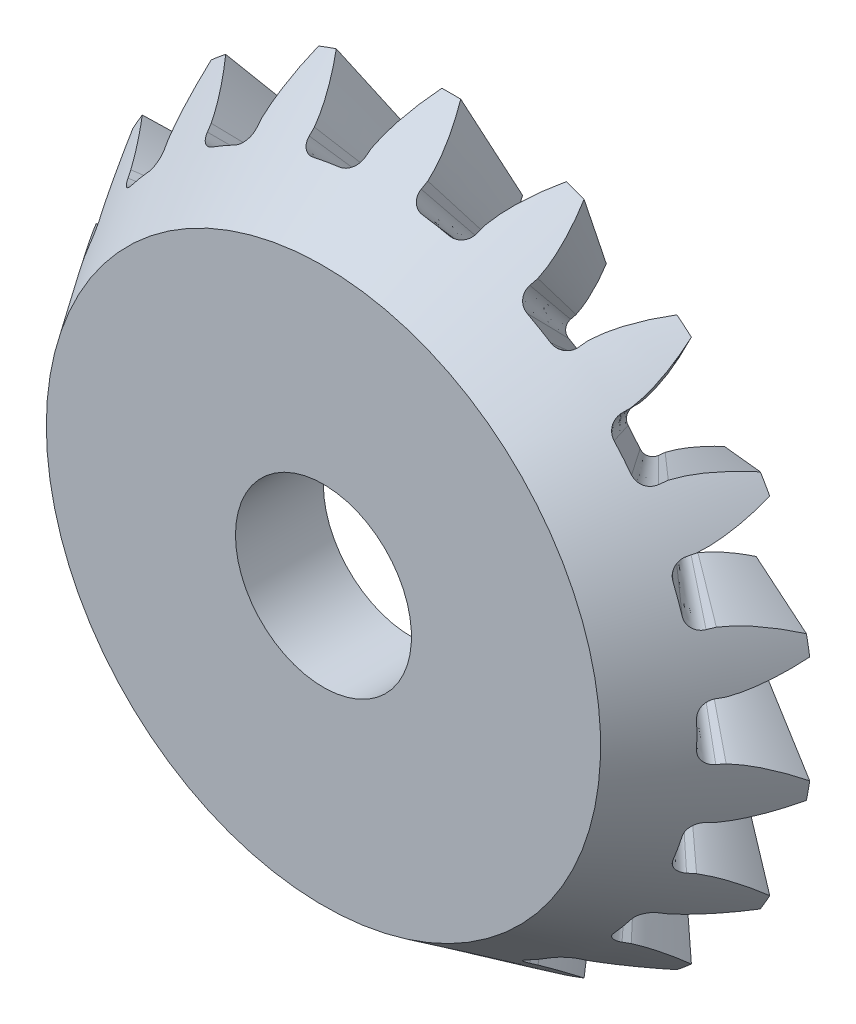
SolidWorks part; units mm, degrees
ref_plane "Front Plane" through (0, 0, 0) normal (0, 0, 1) x (1, 0, 0)
ref_plane "Top Plane" through (0, 0, 0) normal (0, 1, 0) x (1, 0, 0)
ref_plane "Right Plane" through (0, 0, 0) normal (1, 0, 0) x (0, 0, -1)
ref_axis "Gear Axis" through (0, 0, -0.9465) along (0, 0, 1)
sketch "Blank Sketch" plane through (0, 0, 0) normal (0, 1, 0) x (1, 0, 0)
  line L0 (0, 0) -> (0, -18.9291) construction
  line L1 (0, 0) -> (15.75, -10.5) construction
  line L2 (0, 0) -> (10.7577, -7.1718) construction
  line L3 (8.0506, -11.2325) -> (11.1934, -6.5182)
  line L4 (11.1934, -6.5182) -> (16.4727, -9.416)
  line L5 (16.4727, -9.416) -> (12.5987, -15.2269)
  line L6 (12.5987, -15.2269) -> (4, -15.2269)
  line L7 (4, -15.2269) -> (4, -11.2325)
  line L8 (4, -11.2325) -> (8.0506, -11.2325)
  line L9 (15.75, -10.5) -> (16.4727, -9.416) construction
  line L10 (15.75, -10.5) -> (12.5987, -15.2269) construction
  line L11 (10.7577, -7.1718) -> (8.0506, -11.2325) construction
  dimension "Axis" = 18.9291
  dimension "Cone" = 56.31
  dimension "Heel" = 18.9291
  dimension "Toe Cone" = 56.31
  dimension "Toe" = 12.9291
  dimension "Heel Square" = 90
  dimension "Addendum" = 1.3028
  dimension "Root Square" = 90
  dimension "Heel Rim" = 5.6811
  dimension "Toe Square" = 90
  dimension "Toe Rim" = 4.8803
  dimension "Front Square" = 90
  dimension "Face" = 4.927
  dimension "Back" = 8.5987
  dimension "Front" = 4.0506
revolve "Blank" add sketch "Blank Sketch" angle 360 about L0
sketch "Cone Sketch" plane through (0, 0, 0) normal (0, 1, 0) x (1, 0, 0)
  line L0 (0, 0) -> (0, -18.9291) construction
  line L1 (0, 0) -> (17.2061, -11.4707)
  line L2 (0, 0) -> (9.3016, -6.2011)
  dimension "Axis" = 18.9291
  dimension "Toe Cone" = 56.31
  dimension "Heel Cone" = 56.31
  dimension "Heel" = 20.6791
  dimension "Toe" = 11.1791
ref_plane "Heel Plane" through (17.2061, 0, 11.4707) normal (0.8321, 0, 0.5547) x (0.5547, 0, -0.8321)
ref_plane "Toe Plane" through (9.3016, 0, 6.2011) normal (0.8321, 0, 0.5547) x (0.5547, 0, -0.8321)
sketch "Heel Section Sketch" plane through (17.2061, 0, 11.4707) normal (0.8321, 0, 0.5547) x (0.5547, 0, -0.8321)
  line L0 (0, 0) -> (-31.0187, 0) construction
  line L1 (-1.7053, 1.438) -> (-2.0772, 1.4198)
  line L2 (-1.7053, -1.438) -> (-2.0772, -1.4198)
  line L3 (3.1099, 3.9261) -> (3.1099, -3.9261)
  arc A0 (-2.0772, 1.4198) -> (-2.7679, 0.6768) centre (-2.0416, 0.6942) ccw
  arc A1 (-2.7679, -0.6768) -> (-2.0772, -1.4198) centre (-2.0416, -0.6942) ccw
  arc A2 (-2.7679, -0.6768) -> (-2.7679, 0.6768) centre (-31.0187, 0) ccw
  spline S0 degree 4 poles (-1.8404, 1.4185) (-1.8089, 1.4221) (-1.7319, 1.4332) (-1.6753, 1.4426) (-1.5243, 1.4716) (-1.4104, 1.4983) (-1.2549, 1.5367) (-1.1048, 1.5796) (-0.9389, 1.63) (-0.7807, 1.6829) (-0.6197, 1.7397) (-0.4623, 1.7992) (-0.2983, 1.8643) (-0.0976, 1.9482) (0.141, 2.0545) (0.4132, 2.1841) (0.716, 2.3394) (1.011, 2.4999) (1.3074, 2.6722) (1.5907, 2.8442) (1.8847, 3.0345) (2.1502, 3.2115) (2.4519, 3.4264) (2.6832, 3.5939) (3.0044, 3.8418) (3.1539, 3.9604) (3.3382, 4.1103) (3.4429, 4.1974) (3.4923, 4.2389) (3.5194, 4.2617) (3.5333, 4.2734) knots 0 0 0 0 0 0.022117 0.039787 0.058126 0.081614 0.109122 0.13663 0.164138 0.191645 0.219153 0.246661 0.274169 0.305931 0.360947 0.415962 0.470978 0.525993 0.581009 0.636024 0.69104 0.746055 0.801071 0.856086 0.911102 0.955551 0.977775 0.988888 1 1 1 1 1 construction
  spline S1 degree 4 poles (-1.7053, 1.438) (-1.6815, 1.442) (-1.6344, 1.4505) (-1.5243, 1.4716) (-1.4104, 1.4983) (-1.2549, 1.5367) (-1.1048, 1.5796) (-0.9389, 1.63) (-0.7807, 1.6829) (-0.6197, 1.7397) (-0.4623, 1.7992) (-0.2983, 1.8643) (-0.0976, 1.9482) (0.141, 2.0545) (0.4132, 2.1841) (0.716, 2.3394) (1.011, 2.4999) (1.3074, 2.6722) (1.5907, 2.8442) (1.8847, 3.0345) (2.1502, 3.2115) (2.4519, 3.4264) (2.6832, 3.5939) (2.9362, 3.7892) (3.0511, 3.8792) (3.1099, 3.9261) knots 0.022117 0.022117 0.022117 0.022117 0.022117 0.039787 0.058126 0.081614 0.109122 0.13663 0.164138 0.191645 0.219153 0.246661 0.274169 0.305931 0.360947 0.415962 0.470978 0.525993 0.581009 0.636024 0.69104 0.746055 0.801071 0.856086 0.911102 0.911102 0.911102 0.911102 0.911102
  spline S2 degree 4 poles (-1.8404, -1.4185) (-1.8089, -1.4221) (-1.7319, -1.4332) (-1.6753, -1.4426) (-1.5243, -1.4716) (-1.4104, -1.4983) (-1.2549, -1.5367) (-1.1048, -1.5796) (-0.9389, -1.63) (-0.7807, -1.6829) (-0.6197, -1.7397) (-0.4623, -1.7992) (-0.2983, -1.8643) (-0.0976, -1.9482) (0.141, -2.0545) (0.4132, -2.1841) (0.716, -2.3394) (1.011, -2.4999) (1.3074, -2.6722) (1.5907, -2.8442) (1.8847, -3.0345) (2.1502, -3.2115) (2.4519, -3.4264) (2.6832, -3.5939) (3.0044, -3.8418) (3.1539, -3.9604) (3.3382, -4.1103) (3.4429, -4.1974) (3.4923, -4.2389) (3.5194, -4.2617) (3.5333, -4.2734) knots 0 0 0 0 0 0.022117 0.039787 0.058126 0.081614 0.109122 0.13663 0.164138 0.191645 0.219153 0.246661 0.274169 0.305931 0.360947 0.415962 0.470978 0.525993 0.581009 0.636024 0.69104 0.746055 0.801071 0.856086 0.911102 0.955551 0.977775 0.988888 1 1 1 1 1 construction
  spline S3 degree 4 poles (-1.7053, -1.438) (-1.6815, -1.442) (-1.6344, -1.4505) (-1.5243, -1.4716) (-1.4104, -1.4983) (-1.2549, -1.5367) (-1.1048, -1.5796) (-0.9389, -1.63) (-0.7807, -1.6829) (-0.6197, -1.7397) (-0.4623, -1.7992) (-0.2983, -1.8643) (-0.0976, -1.9482) (0.141, -2.0545) (0.4132, -2.1841) (0.716, -2.3394) (1.011, -2.4999) (1.3074, -2.6722) (1.5907, -2.8442) (1.8847, -3.0345) (2.1502, -3.2115) (2.4519, -3.4264) (2.6832, -3.5939) (2.9362, -3.7892) (3.0511, -3.8792) (3.1099, -3.9261) knots 0.022117 0.022117 0.022117 0.022117 0.022117 0.039787 0.058126 0.081614 0.109122 0.13663 0.164138 0.191645 0.219153 0.246661 0.274169 0.305931 0.360947 0.415962 0.470978 0.525993 0.581009 0.636024 0.69104 0.746055 0.801071 0.856086 0.911102 0.911102 0.911102 0.911102 0.911102
  dimension "Root" = 28.2589
  dimension "Fillet" = 0.7265
  dimension "Centre" = 31.0187
sketch "Toe Section Sketch" plane through (9.3016, 0, 6.2011) normal (0.8321, 0, 0.5547) x (0.5547, 0, -0.8321)
  line L0 (0, 0) -> (-16.7687, 0) construction
  line L1 (-0.9219, 0.7774) -> (-1.1229, 0.7675)
  line L2 (-0.9219, -0.7774) -> (-1.1229, -0.7675)
  line L3 (1.6812, 2.1224) -> (1.6812, -2.1224)
  arc A0 (-1.1229, 0.7675) -> (-1.4963, 0.3659) centre (-1.1037, 0.3753) ccw
  arc A1 (-1.4963, -0.3659) -> (-1.1229, -0.7675) centre (-1.1037, -0.3753) ccw
  arc A2 (-1.4963, -0.3659) -> (-1.4963, 0.3659) centre (-16.7687, 0) ccw
  spline S0 degree 4 poles (-0.9968, 0.7665) (-0.9749, 0.7693) (-0.9378, 0.7745) (-0.9043, 0.7801) (-0.8254, 0.7953) (-0.7613, 0.8102) (-0.6792, 0.8306) (-0.5967, 0.854) (-0.5079, 0.8811) (-0.4219, 0.9098) (-0.3352, 0.9405) (-0.2498, 0.9726) (-0.1613, 1.0078) (-0.0527, 1.0532) (0.0762, 1.1107) (0.2234, 1.1807) (0.3871, 1.2647) (0.5465, 1.3514) (0.7068, 1.4446) (0.8599, 1.5376) (1.0188, 1.6404) (1.1625, 1.7362) (1.3255, 1.8523) (1.4506, 1.9429) (1.6241, 2.0768) (1.7153, 2.1491) (1.8305, 2.2431) (1.8808, 2.2855) (1.9096, 2.3098) knots 0 0 0 0 0 0.022117 0.039787 0.058126 0.081614 0.109122 0.13663 0.164138 0.191645 0.219153 0.246661 0.274169 0.305931 0.360947 0.415962 0.470978 0.525993 0.581009 0.636024 0.69104 0.746055 0.801071 0.856086 0.911102 0.955551 1 1 1 1 1 construction
  spline S1 degree 4 poles (-0.9219, 0.7774) (-0.909, 0.7795) (-0.8829, 0.7842) (-0.8254, 0.7953) (-0.7613, 0.8102) (-0.6792, 0.8306) (-0.5967, 0.854) (-0.5079, 0.8811) (-0.4219, 0.9098) (-0.3352, 0.9405) (-0.2498, 0.9726) (-0.1613, 1.0078) (-0.0527, 1.0532) (0.0762, 1.1107) (0.2234, 1.1807) (0.3871, 1.2647) (0.5465, 1.3514) (0.7068, 1.4446) (0.8599, 1.5376) (1.0188, 1.6404) (1.1625, 1.7362) (1.3255, 1.8523) (1.4506, 1.9429) (1.5873, 2.0484) (1.6494, 2.0971) (1.6812, 2.1224) knots 0.022117 0.022117 0.022117 0.022117 0.022117 0.039787 0.058126 0.081614 0.109122 0.13663 0.164138 0.191645 0.219153 0.246661 0.274169 0.305931 0.360947 0.415962 0.470978 0.525993 0.581009 0.636024 0.69104 0.746055 0.801071 0.856086 0.911102 0.911102 0.911102 0.911102 0.911102
  spline S2 degree 4 poles (-0.9968, -0.7665) (-0.9749, -0.7693) (-0.9378, -0.7745) (-0.9043, -0.7801) (-0.8254, -0.7953) (-0.7613, -0.8102) (-0.6792, -0.8306) (-0.5967, -0.854) (-0.5079, -0.8811) (-0.4219, -0.9098) (-0.3352, -0.9405) (-0.2498, -0.9726) (-0.1613, -1.0078) (-0.0527, -1.0532) (0.0762, -1.1107) (0.2234, -1.1807) (0.3871, -1.2647) (0.5465, -1.3514) (0.7068, -1.4446) (0.8599, -1.5376) (1.0188, -1.6404) (1.1625, -1.7362) (1.3255, -1.8523) (1.4506, -1.9429) (1.6241, -2.0768) (1.7153, -2.1491) (1.8305, -2.2431) (1.8808, -2.2855) (1.9096, -2.3098) knots 0 0 0 0 0 0.022117 0.039787 0.058126 0.081614 0.109122 0.13663 0.164138 0.191645 0.219153 0.246661 0.274169 0.305931 0.360947 0.415962 0.470978 0.525993 0.581009 0.636024 0.69104 0.746055 0.801071 0.856086 0.911102 0.955551 1 1 1 1 1 construction
  spline S3 degree 4 poles (-0.9219, -0.7774) (-0.909, -0.7795) (-0.8829, -0.7842) (-0.8254, -0.7953) (-0.7613, -0.8102) (-0.6792, -0.8306) (-0.5967, -0.854) (-0.5079, -0.8811) (-0.4219, -0.9098) (-0.3352, -0.9405) (-0.2498, -0.9726) (-0.1613, -1.0078) (-0.0527, -1.0532) (0.0762, -1.1107) (0.2234, -1.1807) (0.3871, -1.2647) (0.5465, -1.3514) (0.7068, -1.4446) (0.8599, -1.5376) (1.0188, -1.6404) (1.1625, -1.7362) (1.3255, -1.8523) (1.4506, -1.9429) (1.5873, -2.0484) (1.6494, -2.0971) (1.6812, -2.1224) knots 0.022117 0.022117 0.022117 0.022117 0.022117 0.039787 0.058126 0.081614 0.109122 0.13663 0.164138 0.191645 0.219153 0.246661 0.274169 0.305931 0.360947 0.415962 0.470978 0.525993 0.581009 0.636024 0.69104 0.746055 0.801071 0.856086 0.911102 0.911102 0.911102 0.911102 0.911102
  dimension "Root" = 15.2768
  dimension "Fillet" = 0.3927
  dimension "Centre" = 16.7687
loft "Tooth Space" cut profiles "Heel Section Sketch", "Toe Section Sketch"
pattern_circular "Teeth" count 18 over 360 about axis through (0, 0, -0.9465) along (0, 0, 1) of "Tooth Space"
equation "\"No. of Teeth\"= 18"
equation "\"Module\"= 1.75"
equation "\"Bore Diameter\"= 8"
equation "\"Pressure Angle\"= 20"
equation "\"Shaft Angle\"= 90"
equation "\"Mate Teeth\"= 12"
equation "\"Pitch Cone Angle\"= IIF ( ( \"Mate Teeth\" / \"No. of Teeth\" + cos ( \"Shaft Angle\" ) ) > 0 , atn ( sin ( \"Shaft Angle\" ) / ( \"Mate Teeth\" / \"No. of Teeth\" + cos ( \"Shaft Angle\" ) ) ) , 180 + atn ( sin ( \"Shaft Angle\" ) / ( \"Mate Teeth\" / \"No. of Teeth\" + cos ( \"Shaft Angle\" ) ) ) )"
equation "\"Mate Cone Angle\"= \"Shaft Angle\" - \"Pitch Cone Angle\""
equation "\"Addendum\"= IIF ( \"No. of Teeth\" >= \"Mate Teeth\" , 0.54 * \"Module\" + 0.46 * \"Module\" / ( ( \"No. of Teeth\" * cos ( \"Mate Cone Angle\" ) ) / ( \"Mate Teeth\" * cos ( \"Pitch Cone Angle\" ) ) ) , 2 * \"Module\" - ( 0.54 * \"Module\" + 0.46 * \"Module\" / ( ( \"Mate Teeth\" * cos ( \"Pitch Cone Angle\" ) ) / ( \"No. of Teeth\" * cos ( \"Mate Cone Angle\" ) ) ) ) )"
equation "\"Outer Diameter\"= \"No. of Teeth\" * \"Module\" + 2 * \"Addendum\" * cos ( \"Pitch Cone Angle\" )"
equation "\"Pitch Diameter\"= \"No. of Teeth\" * \"Module\""
equation "\"Backlash\"= 0.3 * \"Module\""
equation "\"Arc Length\"= ( ( \"Module\" * pi ) / 2 + \"Backlash\" - 2 * ( \"Addendum\" - \"Module\" ) * tan ( \"Pressure Angle\" ) )"
equation "\"Fillet Radius\"= 0.38 * \"Module\""
equation "\"Mate Addendum\"= 2 * \"Module\" - \"Addendum\""
equation "\"Dedendum\"= 2.188 * \"Module\" - \"Addendum\""
equation "\"Tooth Depth\"= \"Addendum\" + \"Dedendum\""
equation "\"Mate Dedendum\"= 2.188 * \"Module\" - \"Mate Addendum\""
equation "\"Face Width\"= 6"
equation "\"Cone Distance\"= \"Pitch Diameter\" / ( 2 * sin ( \"Pitch Cone Angle\" ) )"
equation "\"Dedendum Angle\"= atn ( \"Dedendum\" / \"Cone Distance\" )"
equation "\"Mate Dedendum Angle\"= atn ( \"Mate Dedendum\" / \"Cone Distance\" )"
equation "\"Face Angle\"= \"Pitch Cone Angle\" + \"Mate Dedendum Angle\""
equation "\"Root Angle\"= \"Pitch Cone Angle\" - \"Dedendum Angle\""
equation "\"Overrun\"= \"Module\""
equation "\"Back Cone Pitch Diameter\"= \"Pitch Diameter\" / cos ( \"Pitch Cone Angle\" )"
equation "\"Back Cone Outer Diameter\"= \"Back Cone Pitch Diameter\" + 2 * \"Addendum\""
equation "\"Root Diameter\"= \"Back Cone Outer Diameter\" - 2 * \"Tooth Depth\""
equation "\"Base Diameter\"= \"Back Cone Pitch Diameter\" * cos ( \"Pressure Angle\" )"
equation "\"Base Radius\"= \"Base Diameter\" / 2"
equation "\"Tooth Thickness\"= \"Module\" * pi - \"Arc Length\""
equation "\"Half Space Angle\"= ( \"Arc Length\" / \"Back Cone Pitch Diameter\" ) * 180 / pi"
equation "\"Involute Fn\"= tan ( \"Pressure Angle\" ) - \"Pressure Angle\" * pi / 180"
equation "\"Flank Offset\"= \"Arc Length\" / \"Back Cone Pitch Diameter\" - \"Involute Fn\""
equation "\"Tip Cap Diameter\"= \"Back Cone Outer Diameter\" + 2 * \"Module\""
equation "\"Flank Start Diameter\"= IIF ( \"Base Diameter\" >= ( \"Root Diameter\" + 3 * \"Fillet Radius\" ) , \"Base Diameter\" , \"Root Diameter\" + 3 * \"Fillet Radius\" )"
equation "\"Involute t1\"= ( abs ( ( \"Flank Start Diameter\" / \"Base Diameter\" ) ^ 2 - 1 ) ) ^ 0.5"
equation "\"Involute t2\"= ( abs ( ( \"Tip Cap Diameter\" / \"Base Diameter\" ) ^ 2 - 1 ) ) ^ 0.5"
equation "\"Flank Arc Radius\"= ( \"Back Cone Pitch Diameter\" / 2 ) * sin ( \"Pressure Angle\" )"
equation "\"Flank Centre Angle\"= \"Half Space Angle\" + \"Pressure Angle\""
equation "\"Heel Distance\"= \"Cone Distance\" + \"Overrun\""
equation "\"Toe Distance\"= \"Cone Distance\" - \"Face Width\" - \"Overrun\""
equation "\"Heel Scale\"= \"Heel Distance\" / \"Cone Distance\""
equation "\"Toe Scale\"= \"Toe Distance\" / \"Cone Distance\""
equation "\"Heel Virtual Radius\"= \"Heel Distance\" * tan ( \"Pitch Cone Angle\" )"
equation "\"Toe Virtual Radius\"= \"Toe Distance\" * tan ( \"Pitch Cone Angle\" )"
equation "\"Axis@Blank Sketch\"= \"Cone Distance\""
equation "\"Cone@Blank Sketch\"= \"Pitch Cone Angle\""
equation "\"Heel@Blank Sketch\"= \"Cone Distance\""
equation "\"Toe Cone@Blank Sketch\"= \"Pitch Cone Angle\""
equation "\"Toe@Blank Sketch\"= \"Cone Distance\" - \"Face Width\""
equation "\"Addendum@Blank Sketch\"= \"Addendum\""
equation "\"Heel Rim@Blank Sketch\"= \"Dedendum\" + \"Module\" / cos ( \"Pitch Cone Angle\" )"
equation "\"Toe Rim@Blank Sketch\"= \"Dedendum\" - \"Face Width\" * tan ( \"Dedendum Angle\" ) + \"Module\" / cos ( \"Pitch Cone Angle\" )"
equation "\"Face@Blank Sketch\"= \"Mate Dedendum Angle\""
equation "\"Back@Blank Sketch\"= \"Cone Distance\" * sin ( \"Pitch Cone Angle\" ) - \"Dedendum\" * cos ( \"Pitch Cone Angle\" ) - \"Module\" - \"Bore Diameter\" / 2"
equation "\"Front@Blank Sketch\"= ( \"Cone Distance\" - \"Face Width\" ) * sin ( \"Pitch Cone Angle\" ) - ( \"Dedendum\" - \"Face Width\" * tan ( \"Dedendum Angle\" ) + \"Module\" / cos ( \"Pitch Cone Angle\" ) ) * cos ( \"Pitch Cone Angle\" ) - \"Bore Diameter\" / 2"
equation "\"Axis@Cone Sketch\"= \"Cone Distance\""
equation "\"Heel Cone@Cone Sketch\"= \"Pitch Cone Angle\""
equation "\"Heel@Cone Sketch\"= \"Heel Distance\""
equation "\"Toe Cone@Cone Sketch\"= \"Pitch Cone Angle\""
equation "\"Toe@Cone Sketch\"= \"Toe Distance\""
equation "\"Centre@Heel Section Sketch\"= \"Heel Virtual Radius\""
equation "\"Root@Heel Section Sketch\"= ( \"Root Diameter\" / 2 ) * \"Heel Scale\""
equation "\"Fillet@Heel Section Sketch\"= ( \"Fillet Radius\" ) * \"Heel Scale\""
equation "\"Centre@Toe Section Sketch\"= \"Toe Virtual Radius\""
equation "\"Root@Toe Section Sketch\"= ( \"Root Diameter\" / 2 ) * \"Toe Scale\""
equation "\"Fillet@Toe Section Sketch\"= ( \"Fillet Radius\" ) * \"Toe Scale\""
equation "\"Count@Teeth\"= \"No. of Teeth\""
